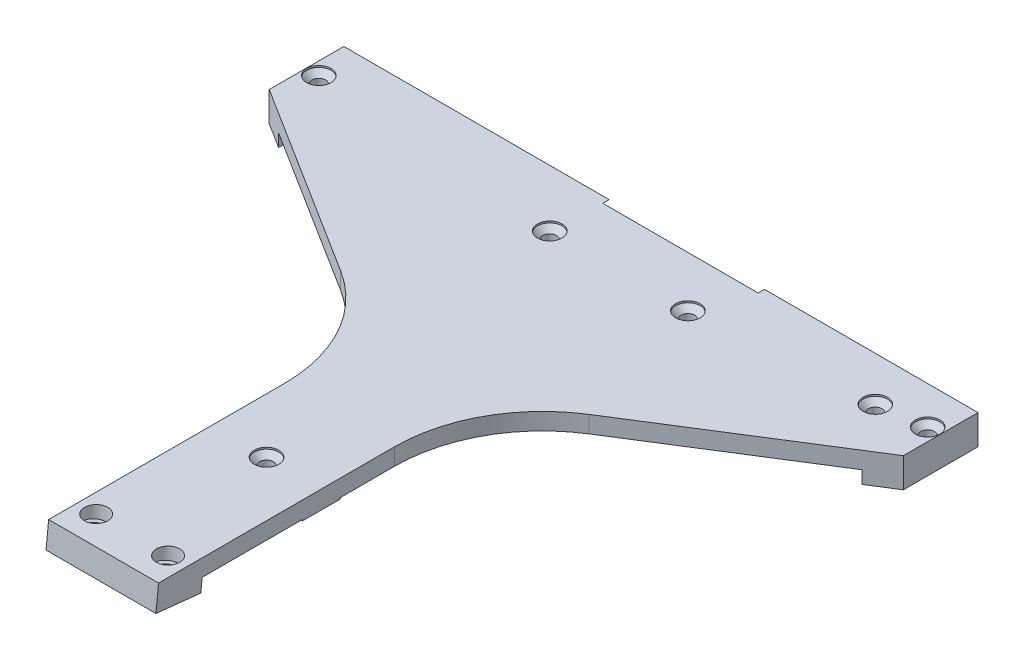
SolidWorks part; units mm, degrees
material "PET"
ref_plane "Plan de face" through (0, 0, 0) normal (0, 0, 1) x (1, 0, 0)
ref_plane "Plan de dessus" through (0, 0, 0) normal (0, 1, 0) x (1, 0, 0)
ref_plane "Plan de droite" through (0, 0, 0) normal (1, 0, 0) x (0, 0, -1)
sketch "Esquisse1" plane through (0, 0, 0) normal (0, 1, 0) x (1, 0, 0)
  line L0 (-13, -130) -> (-13, -76)
  line L1 (-29.3561, -46.379) -> (-75, -17.65)
  line L2 (-75, -17.65) -> (-75, 0)
  line L3 (-75, 0) -> (75, 0)
  line L4 (-13, -130) -> (13, -130)
  line L5 (13, -130) -> (13, -76)
  line L6 (29.3561, -46.379) -> (75, -17.65)
  line L7 (75, -17.65) -> (75, 0)
  line L8 (-75, -17.65) -> (-13, -56.6738) construction
  line L9 (-13, -56.6738) -> (-13, -76) construction
  line L12 (0, -130) -> (0, 0) construction
  arc A0 (-29.3561, -46.379) -> (-13, -76) centre (-48, -76) cw
  arc A3 (29.3561, -46.379) -> (13, -76) centre (48, -76) ccw
  dimension "D5" = 35
  dimension "D1" = 75
  dimension "D2" = 17.65
  dimension "D3" = 150
  dimension "D4" = 26
  dimension "D6" = 54
  dimension "115.21" = 130
extrude "Boss.-Extru.1" add sketch "Esquisse1" along normal blind 4
sketch "Esquisse21" plane through (0, 0, 0) normal (0, -1, 0) x (-1, 0, 0)
  line L0 (75, 0) -> (69, 0)
  line L1 (-75, 0) -> (75, 0) construction
  line L2 (69, 0) -> (69, -21.4265)
  line L3 (75, -17.65) -> (29.3561, -46.379) construction
  line L4 (69, -21.4265) -> (75, -17.65)
  line L5 (75, -17.65) -> (75, 0)
  line L6 (-75, 0) -> (-69, 0)
  line L7 (-69, 0) -> (-69, -21.4265)
  line L8 (-29.3561, -46.379) -> (-75, -17.65) construction
  line L9 (-69, -21.4265) -> (-75, -17.65)
  line L10 (-75, -17.65) -> (-75, 0)
  dimension "D1" = 6
  dimension "D2" = 6
extrude "Boss.-Extru.6" add sketch "Esquisse21" along normal blind 3
hole_wizard "Fraisage pour vis à tête fraisée à 6 pans creux M31" positions "Esquisse5" profile "Esquisse4" countersink size "M3" standard "ISO" end condition up to next
sketch "Esquisse5" plane through (0, 4, 0) normal (0, 1, 0) x (1, 0, 0)
  line L2 (0, 0) -> (0, -130) construction
  line L3 (75, 0) -> (-75, 0) construction
  line L4 (-13, -130) -> (13, -130) construction
  point P0 (61.15, -10.45)
  point P3 (-12.85, -13.45)
  point P6 (19.84, -13.45)
  point P9 (72, -8.91)
  point P15 (-72, -8.91)
  point P44 (0, -93.29)
  dimension "D1" = 72
  dimension "D2" = 36.71
  dimension "D3" = 10.45
  dimension "D4" = 72
  dimension "D5" = 19.84
  dimension "D6" = 79.84
  dimension "D7" = 32.69
  dimension "D8" = 10.85
  dimension "D9" = 8.91
sketch "Esquisse4" plane through (61.15, 4, 10.45) normal (1, 0, 0) x (0, 0, 1)
  line L0 (0, 0) -> (0, 4)
  line L1 (0, 4) -> (1.6, 4)
  line L2 (1.6, 4) -> (1.6, 1.7)
  line L3 (1.6, 1.7) -> (2.9, 0.4)
  line L4 (2.9, 0.4) -> (2.9, 0)
  line L6 (2.9, 0) -> (0, 0)
  line L7 (-1.6, 1.7) -> (-2.9, 0.4) construction
  line L11 (0, -6.35) -> (0, 107.95) construction
  dimension "Diamètre du perçage jusqu'au prochain" = 3.2
  dimension "Profondeur du perçage jusqu'au prochain" = 4
  dimension "Diamètre du fraisage" = 5.8
  dimension "Angle du fraisage" = 90
  dimension "Dégagement de la tête" = 0.4
sketch "Esquisse16" plane through (0, 0, 0) normal (0, 0, -1) x (-1, 0, 0)
  line L0 (16.25, 0) -> (12.25, 4)
  line L2 (-75, 4) -> (75, 4) construction
  line L3 (12.25, 4) -> (-24.5, 4)
  line L4 (-24.5, 4) -> (-28.5, 0)
  line L5 (-69, 0) -> (69, 0) construction
  line L6 (-28.5, 0) -> (16.25, 0)
  dimension "D1" = 16.25
  dimension "D2" = 28.5
  dimension "D3" = 45
  dimension "D4" = 45
extrude "Enlèv. mat.-Extru.9" cut sketch "Esquisse16" against normal blind 1.5
sketch "Esquisse18" plane through (0, 0, 130) normal (0, 0, 1) x (1, 0, 0)
  line L1 (-13, 4) -> (13, 4)
  line L2 (-13, 4) -> (-13, 0)
  line L3 (-13, 0) -> (13, 0)
  line L4 (13, 4) -> (13, 0)
extrude "Boss.-Extru.5" add sketch "Esquisse18" along normal blind 3.5
sketch "Esquisse24" plane through (0, 0, 0) normal (0, -1, 0) x (-1, 0, 0)
  line L0 (13, -76) -> (13, -133.5) construction
  line L1 (13, -97.79) -> (-13, -97.79)
  line L2 (13, -97.79) -> (13, -88.79)
  line L3 (13, -88.79) -> (-13, -88.79)
  line L4 (-13, -97.79) -> (-13, -88.79)
  line L5 (-13, -133.5) -> (-13, -76) construction
  circle A0 centre (0, -93.29) radius 1.6 construction
  circle A1 centre (0, -93.29) radius 1.6
  dimension "D3" = 3.2
  dimension "D1" = 4.5
  dimension "D2" = 9
extrude "Boss.-Extru.7" add sketch "Esquisse24" along normal blind 0.3
sketch "Esquisse25" plane through (0, 0, 0) normal (0, -1, 0) x (-1, 0, 0)
  line L0 (-13, -133.5) -> (-13, -97.79) construction
  line L1 (13, -133.5) -> (-13, -133.5)
  line L2 (13, -133.5) -> (13, -121.5)
  line L3 (13, -121.5) -> (-13, -121.5)
  line L4 (-13, -133.5) -> (-13, -121.5)
  dimension "D1" = 12
extrude "Boss.-Extru.8" add sketch "Esquisse25" along normal blind 3
sketch "Esquisse26" plane through (0, 0, 0) normal (1, 0, 0) x (0, 0, -1)
  line L0 (-121.5, -3) -> (-133.5, -1.7387)
  line L1 (-133.5, 4) -> (-133.5, -3) construction
  line L2 (-133.5, -1.7387) -> (-133.5, -3)
  line L3 (-133.5, -3) -> (-121.5, -3)
  line L5 (-121.5, -3) -> (-121.5, 0) construction
  dimension "D1" = 84
extrude "Enlèv. mat.-Extru.13" cut sketch "Esquisse26" against normal up to next and the other way up to next
sketch "Esquisse34" plane through (0, 0, 0) normal (1, 0, 0) x (0, 0, -1)
  line L0 (-133.5, 4) -> (-131.8249, 4)
  line L1 (-133.5, 4) -> (-76, 4) construction
  line L2 (-131.8249, 4) -> (-132.4397, -1.8502)
  line L3 (-133.5, -1.7387) -> (-121.5, -3) construction
  line L4 (-132.4397, -1.8502) -> (-133.5, -1.7387)
  line L5 (-133.5, -1.7387) -> (-133.5, 4)
  line L6 (-121.5, -3) -> (-132.4397, -1.8502) construction
  dimension "D1" = 11
extrude "Enlèv. mat.-Extru.14" cut sketch "Esquisse34" against normal up to next and the other way up to next
sketch "Esquisse27" plane through (0, -15.5979, 1.6394) normal (0, -0.9945, 0.1045) x (1, 0, 0)
  line L0 (-13, 124.8108) -> (13, 124.8108) construction
  line L1 (-13, 131.5208) -> (-13, 120.5208) construction
  line L2 (13, 131.5208) -> (13, 120.5208) construction
  line L3 (0, 91.6423) -> (0, 124.8108) construction
  line L6 (13, 131.5208) -> (-13, 131.5208) construction
  circle A0 centre (-8.5, 124.8108) radius 1.6
  circle A1 centre (8.5, 124.8108) radius 1.6
  dimension "D2" = 3.2
  dimension "D3" = 17
  dimension "D4" = 8.5
  dimension "D1" = 6.71
sketch "Esquisse30" plane through (0, 0, 0) normal (1, 0, 0) x (0, 0, -1)
  line L0 (-125.7665, -2.5516) -> (-125.0779, 4) construction
  line L1 (-127.3577, -2.3843) -> (-124.1753, -2.7188) construction
  line L2 (-131.8249, 4) -> (-76, 4) construction
  line L3 (-132.4397, -1.8502) -> (-121.5, -3) construction
sketch "Esquisse31" plane through (0, 4, 0) normal (0, 1, 0) x (1, 0, 0)
  line L0 (-13, -125.0779) -> (13, -125.0779) construction
  line L1 (-13, -76) -> (-13, -131.8249) construction
  line L2 (13, -131.8249) -> (13, -76) construction
  line L3 (-8.5, -125.7665) -> (-8.5, -125.0779) construction
  line L4 (8.5, -125.7665) -> (8.5, -125.0779) construction
  point P6 (-8.5, -125.0779)
  point P7 (8.5, -125.0779)
sketch3d "Esquisse3D2"
sketch "Esquisse33" plane through (8.5, 0, 0) normal (1, 0, 0) x (0, 0, -1)
  line L1 (-132.4397, -1.8502) -> (-121.5, -3) construction
  line L6 (-124.9285, 5.4218) -> (-125.7665, -2.5516)
  line L7 (-125.7665, -2.5516) -> (-125.0779, 4) construction
  line L8 (-125.7665, -2.5516) -> (-127.3577, -2.3843)
  line L9 (-126.9396, 1.5938) -> (-128.0833, 1.714)
  line L10 (-127.3577, -2.3843) -> (-126.9396, 1.5938)
  line L11 (-126.9396, 1.5938) -> (-127.8851, 3.6) construction
  line L12 (-127.8851, 3.6) -> (-127.6634, 5.7093)
  line L13 (-127.6634, 5.7093) -> (-124.9285, 5.4218)
  line L14 (-131.8249, 4) -> (-76, 4) construction
  line L15 (-128.0833, 1.714) -> (-127.8851, 3.6)
  point P18 (-127.5115, 1.6539)
  dimension "D1" = 4
  dimension "D2" = 2.75
  dimension "D3" = 1.6
  dimension "D4" = 0.4
revolve "Enlèvement de matière-Révolution1" cut sketch "Esquisse33" angle 360 about L6
mirror "Symétrie1" about plane through (0, 0, 0) normal (1, 0, 0) of "Enlèvement de matière-Révolution1"
sketch "Esquisse37" plane through (13, 0, 0) normal (1, 0, 0) x (0, 0, -1)
  line L0 (-121.5, 0) -> (-121.8119, -2.9672)
  line L1 (-132.4397, -1.8502) -> (-121.5, -3) construction
  line L2 (-121.8119, -2.9672) -> (-121.5, -3)
  line L3 (-121.5, -3) -> (-121.5, 0)
  line L4 (-131.8249, 4) -> (-132.4397, -1.8502) construction
extrude "Enlèv. mat.-Extru.15" cut sketch "Esquisse37" against normal up to next
sketch "Esquisse38" plane through (0, -15.5979, 1.6394) normal (0, -0.9945, 0.1045) x (1, 0, 0)
  line L1 (-13, 131.5208) -> (13, 131.5208)
  line L2 (-13, 131.5208) -> (-13, 120.8344)
  line L3 (-13, 120.8344) -> (13, 120.8344)
  line L4 (13, 131.5208) -> (13, 120.8344)
  circle A0 centre (-8.5, 124.8108) radius 1.6
  circle A1 centre (8.5, 124.8108) radius 1.6
  dimension "D1" = 3.2
  dimension "D2" = 3.2
extrude "Boss.-Extru.10" add sketch "Esquisse38" along normal blind 0.09
